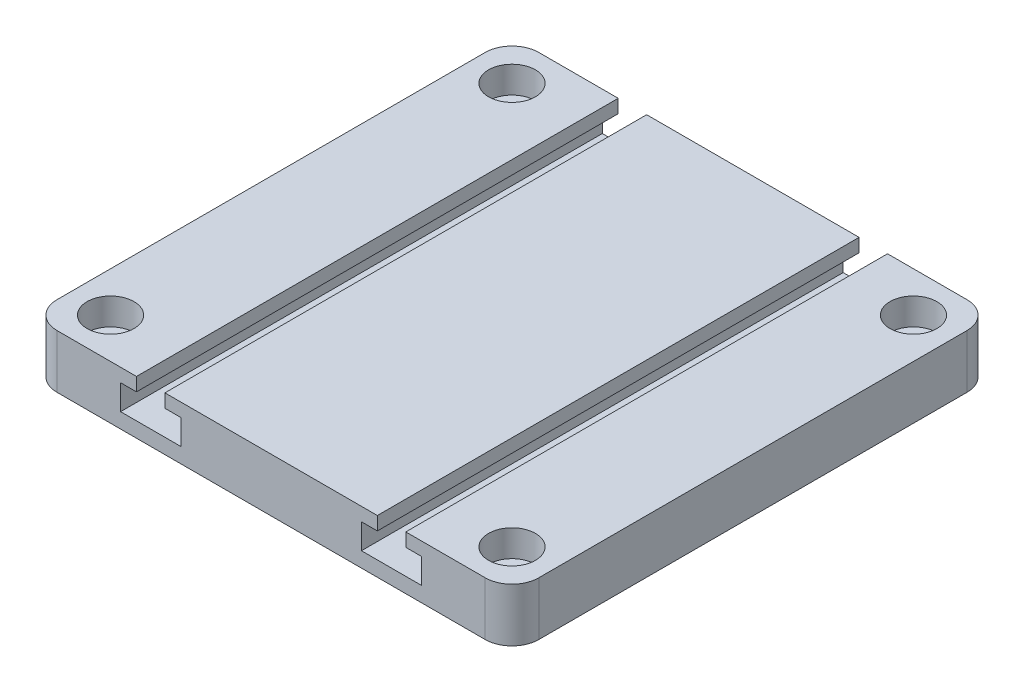
SolidWorks part; units mm, degrees
material "Delrin 2700 NC010, Low Viscosity Acetal Copolymer (SS)"
ref_plane "Front" through (0, 0, 0) normal (0, 0, 1) x (1, 0, 0)
ref_plane "Top" through (0, 0, 0) normal (0, 1, 0) x (1, 0, 0)
ref_plane "Right" through (0, 0, 0) normal (1, 0, 0) x (0, 0, -1)
sketch "Sketch1" plane through (0, 0, 0) normal (0, 1, 0) x (1, 0, 0)
  line L1 (-57.15, 57.15) -> (57.15, 57.15)
  line L2 (-57.15, 57.15) -> (-57.15, -57.15)
  line L3 (-57.15, -57.15) -> (57.15, -57.15)
  line L4 (57.15, 57.15) -> (57.15, -57.15)
  line L5 (-57.15, 57.15) -> (57.15, -57.15) construction
  line L6 (-57.15, -57.15) -> (57.15, 57.15) construction
  point P0 (0, 0)
  dimension "D1" = 114.3
  dimension "D2" = 114.3
extrude "Boss-Extrude1" add sketch "Sketch1" along normal blind 12.7
hole_wizard "CBORE for 1/4 Socket Head Cap Screw1" positions "Sketch2" profile "Sketch3" counterbore size "1/4" standard "ANSI Inch" end condition through all
sketch "Sketch2" plane through (0, 12.7, 0) normal (0, 1, 0) x (1, 0, 0)
  line L1 (-47.625, 47.625) -> (47.625, 47.625) construction
  line L2 (-47.625, 47.625) -> (-47.625, -47.625) construction
  line L3 (-47.625, -47.625) -> (47.625, -47.625) construction
  line L4 (47.625, 47.625) -> (47.625, -47.625) construction
  line L5 (-47.625, 47.625) -> (47.625, -47.625) construction
  line L6 (-47.625, -47.625) -> (47.625, 47.625) construction
  point P0 (-47.625, 47.625)
  point P2 (47.625, 47.625)
  point P4 (47.625, -47.625)
  point P6 (-47.625, -47.625)
  point P108 (0, 0)
  dimension "D1" = 95.25
  dimension "D2" = 95.25
sketch "Sketch3" plane through (-47.625, 12.7, -47.625) normal (1, 0, 0) x (0, 0, 1)
  line L0 (0, 0) -> (0, 12.7)
  line L1 (0, 12.7) -> (3.2639, 12.7)
  line L3 (3.2639, 12.7) -> (3.2639, 6.35)
  line L4 (3.2639, 6.35) -> (5.5562, 6.35)
  line L5 (5.5562, 6.35) -> (5.5562, 0)
  line L7 (5.5562, 0) -> (0, 0)
  line L11 (0, -6.35) -> (0, 107.95) construction
  dimension "Thru Hole Dia." = 6.5278
  dimension "Thru Hole Depth" = 12.7
  dimension "C'Bore Dia." = 11.1125
  dimension "C'Bore Depth" = 6.35
sketch "Sketch4" plane through (0, 0, 57.15) normal (0, 0, 1) x (1, 0, 0)
  line L0 (-31.9484, 12.7) -> (-31.9484, 9.525)
  line L1 (-57.15, 12.7) -> (57.15, 12.7) construction
  line L2 (-31.9484, 9.525) -> (-35.7188, 9.525)
  line L3 (-35.7188, 9.525) -> (-35.7188, 3.5719)
  line L4 (-35.7188, 3.5719) -> (-21.4312, 3.5719)
  line L5 (-21.4312, 3.5719) -> (-21.4312, 9.525)
  line L6 (-21.4312, 9.525) -> (-25.2016, 9.525)
  line L7 (-25.2016, 9.525) -> (-25.2016, 12.7)
  line L8 (0, 0) -> (0, 12.7) construction
  line L9 (-28.575, 3.5719) -> (-28.575, 12.7) construction
  line L10 (28.575, 3.5719) -> (28.575, 12.7) construction
  line L11 (25.2016, 9.525) -> (25.2016, 12.7)
  line L12 (21.4312, 9.525) -> (25.2016, 9.525)
  line L13 (21.4312, 3.5719) -> (21.4312, 9.525)
  line L14 (35.7188, 3.5719) -> (21.4312, 3.5719)
  line L15 (35.7188, 9.525) -> (35.7188, 3.5719)
  line L16 (31.9484, 9.525) -> (35.7188, 9.525)
  line L17 (31.9484, 12.7) -> (31.9484, 9.525)
  line L18 (-31.9484, 12.7) -> (-25.2016, 12.7)
  line L19 (25.2016, 12.7) -> (31.9484, 12.7)
  line L20 (-57.15, 0) -> (57.15, 0) construction
  dimension "D1" = 14.2875
  dimension "D2" = 6.7469
  dimension "D3" = 3.175
  dimension "D4" = 57.15
  dimension "D5" = 5.9531
  dimension "D6" = 3.5719
extrude "T-SLOT CUT WITH MCMASTER 8789A16 BIT" cut sketch "Sketch4" against normal through all
fillet "Fillet1" radius 6.35 4 edges at (-57.15, 6.35, 57.15) (57.15, 6.35, 57.15) (57.15, 6.35, -57.15) (-57.15, 6.35, -57.15)
